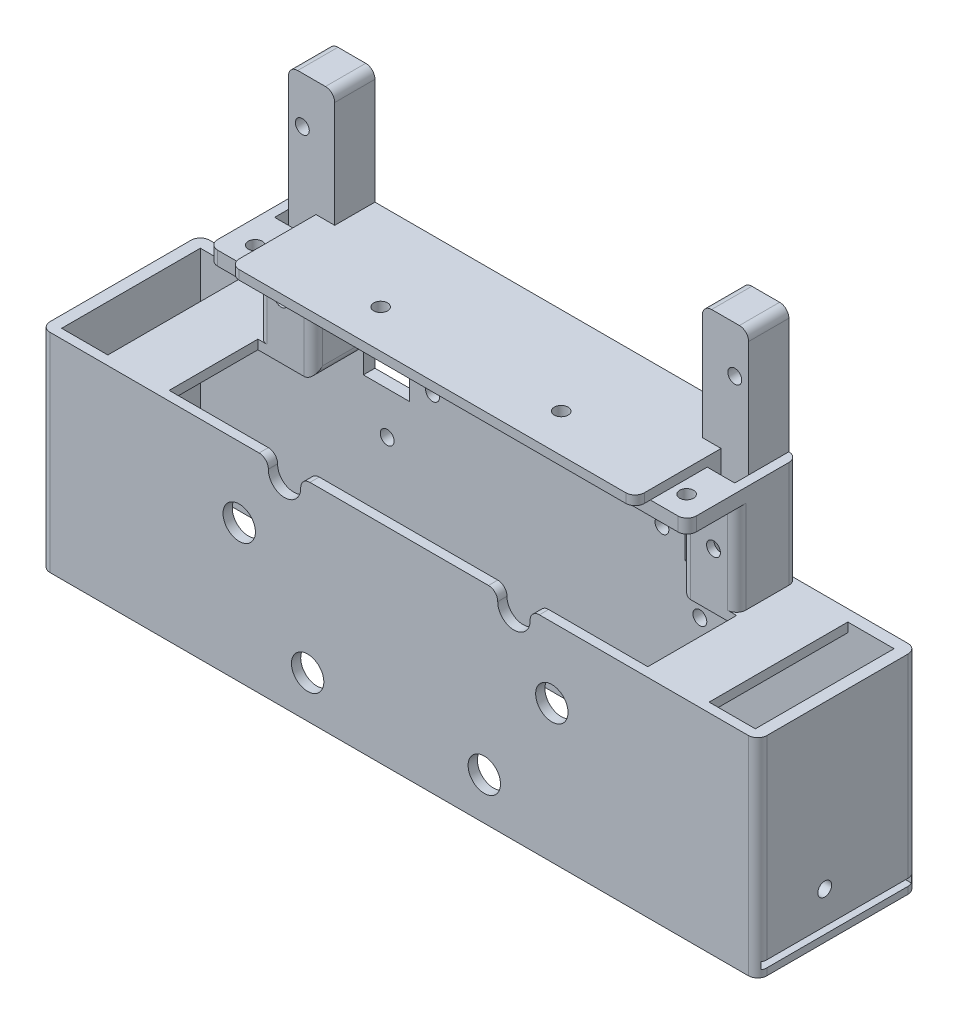
SolidWorks part; units mm, degrees
ref_plane "前视基准面" through (0, 0, 0) normal (0, 0, 1) x (1, 0, 0)
ref_plane "上视基准面" through (0, 0, 0) normal (0, 1, 0) x (1, 0, 0)
ref_plane "右视基准面" through (0, 0, 0) normal (1, 0, 0) x (0, 0, -1)
other "Configuration Table"
sketch "草图1" plane through (0, 0, 0) normal (0, 0, 1) x (1, 0, 0)
  line L0 (7.95, 3) -> (7.95, 5)
  line L1 (0, 0) -> (103.5, 0)
  line L2 (0, 0) -> (0, 3)
  line L3 (0, 3) -> (103.5, 3)
  line L4 (103.5, 0) -> (103.5, 3)
  line L5 (7.95, 5) -> (95.55, 5)
  line L6 (95.55, 5) -> (95.55, 3)
  line L7 (12, 3) -> (12, 30) construction
  line L8 (12, 30) -> (91.5, 30) construction
  line L9 (91.5, 30) -> (91.5, 3) construction
  line L10 (91.5, 30) -> (101.5, 30)
  line L11 (101.5, 30) -> (101.5, 3)
  line L12 (91.5, 30) -> (91.5, 5)
  line L13 (103.5, 0) -> (103.5, -46.5)
  line L14 (91.5, 0) -> (91.5, -46.5)
  line L15 (91.5, -46.5) -> (103.5, -46.5)
  line L16 (101.5, 3) -> (101.5, -46.5)
  line L17 (51.75, -46.5) -> (51.75, -16.5)
  line L18 (51.75, -16.5) -> (91.5, -16.5)
  line L19 (51.75, -46.5) -> (91.5, -46.5)
  line L20 (51.75, -16.5) -> (51.75, 0)
  line L21 (66.75, -16.5) -> (66.75, 0)
  line L22 (91.5, -16.5) -> (101.5, -16.5)
  line L23 (51.75, 5) -> (51.75, 0) construction
  line L24 (51.75, 5) -> (51.75, 0)
  line L25 (51.75, -20) -> (103.5, -20)
  line L26 (103.5, -20) -> (103.5, -65)
  line L27 (103.5, -65) -> (51.75, -65)
  line L28 (51.75, -65) -> (51.75, -20)
  line L29 (91.5, 5) -> (91.5, 0)
  line L30 (91.5, -46.5) -> (91.5, -65)
  line L31 (101.5, -46.5) -> (101.5, -65)
  line L32 (101.5, -16.5) -> (103.5, -16.5)
  line L33 (51.75, 5) -> (51.75, 30)
  line L34 (51.75, 30) -> (91.5, 30)
  point P7 (51.75, 5)
  point P10 (51.75, 3)
  point P14 (51.75, 30)
  dimension "D1" = 103.5
  dimension "D2" = 3
  dimension "D3" = 87.6
  dimension "D4" = 2
  dimension "D5" = 79.5
  dimension "D6" = 10
  dimension "D7" = 27
  dimension "D8" = 49.5
  dimension "D9" = 30
  dimension "D10" = 15
  dimension "D11" = 45
  dimension "D12" = 20
extrude "凸台-拉伸1" add sketch "草图1" along normal blind 19 contours L3 L29 L1 L16 | L3 L16 L1 L4 region at (96.5, 1.5, 0) region at (102.5, 1.5, 0)
extrude "凸台-拉伸2" add sketch "草图1<13>" along normal blind 13.2 from offset 5.8 contours L29 L3 L24 L1 region at (71.625, 1.5, 0)
sketch "草图1<13>" plane through (0, 0, 0) normal (0, 0, 1) x (1, 0, 0) same geometry as "草图1"
extrude "凸台-拉伸3" add sketch "草图1<14>" along normal blind 22.3 contours L5 L29 L3 L6 region at (93.525, 4, 0)
sketch "草图1<14>" plane through (0, 0, 0) normal (0, 0, 1) x (1, 0, 0) same geometry as "草图1"
extrude "凸台-拉伸4" add sketch "草图1<15>" along normal blind 16.5 from offset 5.8 contours L29 L5 L24 L3 region at (71.625, 4, 0)
sketch "草图1<15>" plane through (0, 0, 0) normal (0, 0, 1) x (1, 0, 0) same geometry as "草图1"
extrude "凸台-拉伸5" add sketch "草图1<16>" along normal blind 3.7 contours L10 L12 L5 L6 L3 L11 | L14 L22 L16 L1 | L14 L25 L16 L22 | L25 L14 L15 L16 | L16 L25 L13 L1 | L25 L16 L15 L13 | L15 L30 L27 L26 | L15 L31 L27 L26 | L32 L16 L25 L13 region at (96.592, 16.8866, 0) region at (96.5, -8.25, 0) region at (102.5, -8.25, 0) region at (96.5, -18.25, 0) region at (102.5, -18.25, 0) region at (96.5, -33.25, 0) region at (102.5, -33.25, 0) region at (96.5, -55.75, 0) region at (102.5, -55.75, 0)
sketch "草图1<16>" plane through (0, 0, 0) normal (0, 0, 1) x (1, 0, 0) same geometry as "草图1"
extrude "凸台-拉伸6" add sketch "草图1<20>" along normal blind 2.5 from surface contours L25 L17 L19 L14 | L30 L19 L28 L27 | L18 L21 L1 L20 | L17 L25 L14 L18 | L21 L18 L14 L1 region at (59.25, -8.25, 0) region at (79.125, -8.25, 0) region at (71.625, -18.25, 0) region at (71.625, -33.25, 0) region at (71.625, -55.75, 0) starting at face at (71.625, 2.5, 5.8)
sketch "草图1<20>" plane through (0, 0, 0) normal (0, 0, 1) x (1, 0, 0) same geometry as "草图1"
extrude "凸台-拉伸8" add sketch "草图1<23>" along normal up to surface (8.3 mm away) from surface contours L25 L14 L15 L16 | L31 L15 L30 L27 | L14 L25 L16 L22 | L32 L16 L25 L13 | L25 L16 L15 L13 | L15 L31 L27 L26 | L14 L22 L16 L1 | L16 L32 L13 L1 region at (96.5, -8.25, 0) region at (102.5, -8.25, 0) region at (96.5, -18.25, 0) region at (102.5, -18.25, 0) region at (96.5, -33.25, 0) region at (102.5, -33.25, 0) region at (96.5, -55.75, 0) region at (102.5, -55.75, 0) up to face at (71.625, -32.5, 8.3) starting at face at (97.5, -32.5, 3.7)
sketch "草图1<23>" plane through (0, 0, 0) normal (0, 0, 1) x (1, 0, 0) same geometry as "草图1"
sketch "草图2" plane through (0, -65, 0) normal (0, -1, 0) x (1, 0, 0)
  line L4 (51.75, 8.3) -> (103.5, 8.3)
  line L5 (103.5, 8.3) -> (103.5, 19)
  line L6 (91.5, 0) -> (103.5, 0)
  line L7 (103.5, 0) -> (103.5, 8.3)
  line L8 (103.5, 8.3) -> (51.75, 8.3)
  line L9 (51.75, 8.3) -> (51.75, 5.8)
  line L10 (51.75, 5.8) -> (91.5, 5.8)
  line L11 (91.5, 5.8) -> (91.5, 0)
  line L12 (91.5, 0) -> (103.5, 0)
  line L13 (103.5, 0) -> (103.5, 8.3)
  line L14 (103.5, 8.3) -> (51.75, 8.3)
  line L15 (51.75, 8.3) -> (51.75, 5.8)
  line L16 (51.75, 5.8) -> (91.5, 5.8)
  line L17 (91.5, 5.8) -> (91.5, 0)
  line L18 (103.5, 19) -> (51.75, 19)
  line L19 (51.75, 19) -> (51.75, 8.3)
  line L20 (51.75, 8.3) -> (103.5, 8.3)
  line L21 (103.5, 8.3) -> (103.5, 19)
  line L22 (103.5, 19) -> (51.75, 19)
  line L23 (51.75, 19) -> (51.75, 8.3)
  dimension "D2" = 8.3
  dimension "D1" = 0
  dimension "D3" = 0
extrude "凸台-拉伸9" add sketch "草图1<25>" along normal blind 2 from offset 27.5 separate body contours L25 L17 L19 L14 | L30 L19 L28 L27 | L31 L15 L30 L27 | L25 L14 L15 L16 region at (71.625, -33.25, 0) region at (96.5, -33.25, 0) region at (71.625, -55.75, 0) region at (96.5, -55.75, 0)
sketch "草图1<25>" plane through (0, 0, 0) normal (0, 0, 1) x (1, 0, 0) same geometry as "草图1"
sketch "草图3" plane through (0, 0, 29.5) normal (0, 0, 1) x (1, 0, 0)
  line L0 (101.5, -20) -> (126.75, -20)
  line L1 (126.75, -20) -> (126.75, -65)
  line L2 (126.75, -65) -> (101.5, -65)
  line L3 (126.75, -20) -> (129.25, -20)
  line L4 (51.75, -65) -> (101.5, -65)
  line L5 (101.5, -65) -> (101.5, -20)
  line L6 (101.5, -20) -> (51.75, -20)
  line L7 (51.75, -20) -> (51.75, -65)
  line L8 (51.75, -65) -> (101.5, -65)
  line L9 (101.5, -65) -> (101.5, -20)
  line L10 (101.5, -20) -> (51.75, -20)
  line L11 (51.75, -20) -> (51.75, -65)
  line L12 (129.25, -20) -> (129.25, -65)
  line L13 (129.25, -65) -> (126.75, -65)
  line M7 (101.5, -65) -> (101.5, -20)
  dimension "D2" = 75
  dimension "D3" = 2.5
  dimension "D1" = 0
extrude "凸台-拉伸11" add sketch "草图3" against normal up to surface (2 mm away) contours L2 L1 L0 M7 region at (114.125, -42.5, 29.5) up to face at (76.625, -42.5, 27.5)
extrude "凸台-拉伸12" add sketch "草图3<4>" against normal up to surface (29.5 mm away) contours L13 L12 L3 L1 region at (128, -42.5, 29.5) up to face at (98.8333, -10.6667, 0)
sketch "草图3<4>" plane through (0, 0, 29.5) normal (0, 0, 1) x (1, 0, 0) same geometry as "草图3"
sketch "草图5" plane through (129.25, 0, 0) normal (1, 0, 0) x (0, 0, -1)
  line L4 (-29.5, -65) -> (0, -65)
  line L5 (0, -65) -> (0, -20)
  line L6 (0, -20) -> (-29.5, -20)
  line L7 (-29.5, -20) -> (-29.5, -65)
  line L8 (-29.5, -65) -> (0, -65)
  line L9 (0, -65) -> (0, -20)
  line L10 (0, -20) -> (-29.5, -20)
  line L11 (-29.5, -20) -> (-29.5, -65)
  line L16 (0, -65) -> (0, 3)
  line L17 (0, 3) -> (-19, 3)
  line L18 (-19, 3) -> (-19, 0)
  line L19 (-19, 0) -> (-8.3, 0)
  line L22 (-8.3, 0) -> (-8.3, -65)
  line L23 (-8.3, -65) -> (0, -65)
  line L24 (0, -65) -> (0, 3)
  line L25 (0, 3) -> (-19, 3)
  line L26 (-19, 3) -> (-19, 0)
  line L27 (-19, 0) -> (-8.3, 0)
  line L30 (-8.3, 0) -> (-8.3, -65)
  line L31 (-8.3, -65) -> (0, -65)
  line M14 (0, -65) -> (0, -20)
  line M15 (0, -20) -> (-29.5, -20)
  dimension "D1" = 0
  dimension "D2" = 0
extrude "凸台-拉伸13" add sketch "草图5" against normal up to surface (25.75 mm away) from surface contours L30 L8 M15 M14 region at (129.25, -42.5, 4.15) up to face at (103.5, -20.6667, 9.1) starting at face at (126.75, -42.5, 13.75)
sketch "草图6" plane through (0, 5, 0) normal (0, 1, 0) x (1, 0, 0)
  line L0 (51.75, -14) -> (103.5, -14) construction
  line L1 (95.55, -6.7) -> (101.5, -6.7)
  line L3 (101.5, -6.7) -> (101.5, -3.7)
  line L6 (95.55, -3.7) -> (91.5, -3.7)
  line L7 (91.5, -3.7) -> (91.5, -5.8)
  line L8 (91.5, -5.8) -> (51.75, -5.8)
  line L9 (51.75, -5.8) -> (51.75, -22.3)
  line L10 (51.75, -22.3) -> (95.55, -22.3)
  line L11 (95.55, -22.3) -> (95.55, -3.7)
  line L12 (95.55, -3.7) -> (91.5, -3.7)
  line L13 (91.5, -3.7) -> (91.5, -5.8)
  line L14 (91.5, -5.8) -> (51.75, -5.8)
  line L15 (51.75, -5.8) -> (51.75, -22.3)
  line L16 (51.75, -22.3) -> (95.55, -22.3)
  line L17 (95.55, -22.3) -> (95.55, -3.7)
  line L18 (101.5, 0) -> (101.5, -3.7)
  line L19 (101.5, -3.7) -> (95.55, -3.7)
  line L20 (95.55, -3.7) -> (95.55, -19)
  line L21 (95.55, -19) -> (103.5, -19)
  line L22 (103.5, -19) -> (103.5, 0)
  line L23 (103.5, 0) -> (101.5, 0)
  line L24 (101.5, 0) -> (101.5, -3.7)
  line L25 (101.5, -3.7) -> (95.55, -3.7)
  line L26 (95.55, -3.7) -> (95.55, -19)
  line L27 (95.55, -19) -> (103.5, -19)
  line L28 (103.5, -19) -> (103.5, 0)
  line L29 (103.5, 0) -> (101.5, 0)
  circle A0 centre (71.27, -14) radius 1.5
  circle A1 centre (98.39, -14) radius 1.5
  line M18 (95.55, -22.3) -> (95.55, -3.7)
  dimension "D5" = 3
  dimension "D6" = 3
  dimension "D3" = 8.3
  dimension "D4" = 8.2
  dimension "D7" = 19.52
  dimension "D8" = 27.12
  dimension "D9" = 3
  dimension "D1" = 0
  dimension "D2" = 0
extrude "切除-拉伸1" cut sketch "草图6" against normal up to next contours A0 L0 | L0 A0 | A1 L0 | L0 A1 | L3 L25 L1 M18 region at (98.39, 5, 14.6366) region at (98.39, 5, 13.3634) region at (71.27, 5, 14.6366) region at (71.27, 5, 13.3634) region at (98.525, 5, 5.2)
ref_plane "基准面1" through (51.75, 0, 0) normal (-1, 0, 0) x (0, 0, 1)
sketch "草图7" plane through (0, -20, 0) normal (0, 1, 0) x (1, 0, 0)
  line L0 (103.5, -8.3) -> (103.5, -27.5)
  line L1 (116.75, -8.3) -> (116.75, -27.5)
  line L8 (103.5, 0) -> (103.5, -8.3)
  line L9 (103.5, -8.3) -> (126.75, -8.3)
  line L10 (126.75, -8.3) -> (126.75, -27.5)
  line L11 (126.75, -27.5) -> (51.75, -27.5)
  line L12 (51.75, -27.5) -> (51.75, -29.5)
  line L13 (51.75, -29.5) -> (129.25, -29.5)
  line L14 (129.25, -29.5) -> (129.25, 0)
  line L15 (129.25, 0) -> (103.5, 0)
  line L16 (103.5, 0) -> (103.5, -8.3)
  line L17 (103.5, -8.3) -> (126.75, -8.3)
  line L18 (126.75, -8.3) -> (126.75, -27.5)
  line L19 (126.75, -27.5) -> (51.75, -27.5)
  line L20 (51.75, -27.5) -> (51.75, -29.5)
  line L21 (51.75, -29.5) -> (129.25, -29.5)
  line L22 (129.25, -29.5) -> (129.25, 0)
  line L23 (129.25, 0) -> (103.5, 0)
  line M11 (103.5, -8.3) -> (126.75, -8.3)
  line M13 (126.75, -27.5) -> (51.75, -27.5)
  dimension "D2" = 10
  dimension "D1" = 0
extrude "凸台-拉伸14" add sketch "草图7" against normal blind 2 contours L1 L0 M11 M13 region at (110.125, -20, 17.9)
sketch "草图9" plane through (0, 0, 0) normal (0, 0, -1) x (-1, 0, 0)
  line L7 (-51.75, -5) -> (-76.55, -5) construction
  line L8 (-101.5, 30) -> (-101.5, 3)
  line L9 (-101.5, 3) -> (-103.5, 3)
  line L10 (-103.5, 3) -> (-103.5, -20)
  line L11 (-103.5, -20) -> (-129.25, -20)
  line L12 (-129.25, -20) -> (-129.25, -65)
  line L13 (-129.25, -65) -> (-91.5, -65)
  line L14 (-91.5, -65) -> (-91.5, 30)
  line L15 (-91.5, 30) -> (-101.5, 30)
  line L16 (-101.5, 30) -> (-101.5, 3)
  line L17 (-101.5, 3) -> (-103.5, 3)
  line L18 (-103.5, 3) -> (-103.5, -20)
  line L19 (-103.5, -20) -> (-129.25, -20)
  line L20 (-129.25, -20) -> (-129.25, -65)
  line L21 (-129.25, -65) -> (-91.5, -65)
  line L22 (-91.5, -65) -> (-91.5, 30)
  line L23 (-91.5, 30) -> (-101.5, 30)
  line L24 (-76.55, -5) -> (-76.55, -22.1) construction
  line L25 (-76.55, -22.1) -> (-51.75, -22.1) construction
  line L26 (-91.5, -26.1) -> (-51.75, -26.1) construction
  line L28 (-91.5, 5) -> (-91.5, -65)
  line L33 (-91.5, -65) -> (-51.75, -65)
  line L34 (-51.75, -65) -> (-51.75, 5)
  line L35 (-51.75, 5) -> (-91.5, 5)
  line L36 (-91.5, 5) -> (-91.5, -65)
  line L41 (-91.5, -65) -> (-51.75, -65)
  line L42 (-51.75, -65) -> (-51.75, 5)
  line L43 (-51.75, 5) -> (-91.5, 5)
  circle A4 centre (-76.55, -5) radius 1.5
  circle A5 centre (-76.55, -22.1) radius 1.5
  dimension "D13" = 3
  dimension "D14" = 3
  dimension "D15" = 10
  dimension "D16" = 17.1
  dimension "D17" = 24.8
  dimension "D18" = 4
  dimension "D1" = 0
  dimension "D7" = 0
sketch "草图17" plane through (0, 0, 27.5) normal (0, 0, -1) x (-1, 0, 0)
  line L1 (-103.5, -22) -> (-51.75, -22)
  line L9 (-51.75, -65) -> (-51.75, -20)
  line L10 (-51.75, -65) -> (-51.75, -20)
  line L15 (-51.75, -20) -> (-103.5, -20)
  line L16 (-103.5, -20) -> (-103.5, -22)
  line L17 (-103.5, -22) -> (-116.75, -22)
  line L18 (-116.75, -22) -> (-116.75, -20)
  line L19 (-116.75, -20) -> (-126.75, -20)
  line L20 (-126.75, -20) -> (-126.75, -65)
  line L21 (-126.75, -65) -> (-51.75, -65)
  line L29 (-51.75, -20) -> (-103.5, -20)
  line L30 (-103.5, -20) -> (-103.5, -22)
  line L31 (-103.5, -22) -> (-116.75, -22)
  line L32 (-116.75, -22) -> (-116.75, -20)
  line L33 (-116.75, -20) -> (-126.75, -20)
  line L34 (-126.75, -20) -> (-126.75, -65)
  line L35 (-126.75, -65) -> (-51.75, -65)
  line M22 (-103.5, -22) -> (-116.75, -22)
  line M23 (-116.75, -22) -> (-116.75, -20)
  line M24 (-116.75, -20) -> (-126.75, -20)
  line M25 (-126.75, -20) -> (-126.75, -65)
  line M26 (-126.75, -65) -> (-51.75, -65)
  line M52 (-51.75, -65) -> (-51.75, -20)
  dimension "D1" = 0
extrude "凸台-拉伸15" add sketch "草图1<29>" along normal up to surface (5.8 mm away) contours L34 L33 L5 L12 | L30 L19 L28 L27 | L25 L17 L19 L14 | L21 L18 L14 L1 | L18 L21 L1 L20 | L29 L3 L24 L1 | L29 L5 L24 L3 | L17 L25 L14 L18 region at (71.625, 4, 0) region at (71.625, 1.5, 0) region at (71.625, 17.5, 0) region at (59.25, -8.25, 0) region at (79.125, -8.25, 0) region at (71.625, -18.25, 0) region at (71.625, -33.25, 0) region at (71.625, -55.75, 0) up to face at (71.625, -30, 5.8)
sketch "草图1<29>" plane through (0, 0, 0) normal (0, 0, 1) x (1, 0, 0) same geometry as "草图1"
extrude "切除-拉伸10" cut sketch "草图17" along normal blind 5.8 from surface contours L1 M22 M23 M24 M25 M26 M52 region at (89.4503, -43.3613, 27.5) starting at face at (100.1111, -26, 8.3)
extrude "切除-拉伸12" cut sketch "草图9" against normal through all contours A4 | A5 region at (76.55, -5, 0) region at (76.55, -22.1, 0)
sketch "草图21" plane through (0, 0, 0) normal (0, 0, -1) x (-1, 0, 0)
  line L8 (-101.5, 30) -> (-101.5, 3)
  line L9 (-101.5, 3) -> (-103.5, 3)
  line L10 (-103.5, 3) -> (-103.5, -20)
  line L11 (-103.5, -20) -> (-129.25, -20)
  line L12 (-129.25, -20) -> (-129.25, -65)
  line L13 (-129.25, -65) -> (-51.75, -65)
  line L14 (-51.75, -65) -> (-51.75, 30)
  line L15 (-51.75, 30) -> (-101.5, 30)
  line L16 (-101.5, 30) -> (-101.5, 3)
  line L17 (-101.5, 3) -> (-103.5, 3)
  line L18 (-103.5, 3) -> (-103.5, -20)
  line L19 (-103.5, -20) -> (-129.25, -20)
  line L20 (-129.25, -20) -> (-129.25, -65)
  line L21 (-129.25, -65) -> (-51.75, -65)
  line L22 (-51.75, -65) -> (-51.75, 30)
  line L23 (-51.75, 30) -> (-101.5, 30)
  circle A3 centre (-76.55, -22.1) radius 1.5 construction
  circle A4 centre (-76.55, -5) radius 1.5 construction
  circle A9 centre (-76.55, -22.1) radius 1.5
  circle A10 centre (-76.55, -5) radius 1.5
  dimension "D1" = 0
extrude "凸台-拉伸16" add sketch "草图21" along normal blind 5
extrude "切除-拉伸14" cut sketch "草图17<10>" along normal blind 5 from surface contours L1 M22 M23 M24 M25 M26 M52 region at (89.4503, -43.3613, 27.5) starting at face at (92.95, -32.45, 2.5)
sketch "草图17<10>" plane through (0, 0, 27.5) normal (0, 0, -1) x (-1, 0, 0) same geometry as "草图17"
sketch "草图24" plane through (0, 0, 8.3) normal (0, 0, 1) x (1, 0, 0)
  line L1 (95.55, -22) -> (101.5, -22) construction
  line L2 (101.5, -22) -> (101.5, 3) construction
  line L3 (101.5, 3) -> (101.5, 30) construction
  line L4 (101.5, 30) -> (91.5, 30) construction
  line L5 (91.5, 30) -> (91.5, 5) construction
  line L6 (78.0467, -22) -> (103.5, -22)
  line L7 (103.5, -22) -> (103.5, -20)
  line L8 (103.5, -20) -> (103.5, 0)
  line L9 (103.5, 0) -> (51.75, 0)
  line L10 (51.75, 0) -> (51.75, -22)
  line L11 (51.75, -22) -> (75.0533, -22)
  line L12 (78.0467, -22) -> (103.5, -22)
  line L13 (103.5, -22) -> (103.5, -20)
  line L14 (103.5, -20) -> (103.5, 0)
  line L15 (103.5, 0) -> (51.75, 0)
  line L16 (51.75, 0) -> (51.75, -22)
  line L17 (51.75, -22) -> (75.0533, -22)
  line L18 (91.5, 5) -> (95.55, 5) construction
  line L19 (95.55, 5) -> (95.55, -22) construction
  line L20 (95.55, 5) -> (51.75, 5) construction
  line L21 (51.75, 5) -> (51.75, 3) construction
  line L22 (51.75, 3) -> (95.55, 3) construction
  line L23 (95.55, 3) -> (95.55, 5) construction
  line L24 (95.55, 3) -> (51.75, 3) construction
  line L25 (51.75, 3) -> (51.75, 0) construction
  line L26 (51.75, 0) -> (103.5, 0) construction
  line L27 (103.5, 0) -> (103.5, 3) construction
  line L28 (103.5, 3) -> (95.55, 3) construction
  line L29 (51.75, 30) -> (51.75, 5) construction
  line L30 (51.75, 5) -> (91.5, 5) construction
  line L31 (91.5, 5) -> (91.5, 30) construction
  line L32 (91.5, 30) -> (51.75, 30) construction
  line L33 (95.55, -22) -> (101.5, -22)
  line L34 (101.5, -22) -> (101.5, 3)
  line L35 (101.5, 3) -> (101.5, 30)
  line L36 (101.5, 30) -> (91.5, 30)
  line L37 (91.5, 30) -> (91.5, 5)
  line L38 (91.5, 5) -> (95.55, 5)
  line L39 (95.55, 5) -> (95.55, -22)
  line L40 (95.55, 5) -> (51.75, 5)
  line L41 (51.75, 5) -> (51.75, 3)
  line L42 (51.75, 3) -> (95.55, 3)
  line L43 (95.55, 3) -> (95.55, 5)
  line L44 (95.55, 3) -> (51.75, 3)
  line L45 (51.75, 3) -> (51.75, 0)
  line L46 (51.75, 0) -> (103.5, 0)
  line L47 (103.5, 0) -> (103.5, 3)
  line L48 (103.5, 3) -> (95.55, 3)
  line L49 (51.75, 30) -> (51.75, 5)
  line L50 (51.75, 5) -> (91.5, 5)
  line L51 (91.5, 5) -> (91.5, 30)
  line L52 (91.5, 30) -> (51.75, 30)
  line L53 (91.5, 0) -> (91.5, -22)
  circle A0 centre (76.55, -5) radius 1.5 construction
  arc A1 (78.0467, -22) -> (75.0533, -22) centre (76.55, -22.1) ccw
  arc A2 (78.0467, -22) -> (75.0533, -22) centre (76.55, -22.1) ccw
  circle A3 centre (76.55, -5) radius 1.5
  circle M9 centre (76.55, -5) radius 1.5
  arc M10 (75.0533, -22) -> (78.0467, -22) centre (76.55, -22.1) cw
  line M11 (78.0467, -22) -> (103.5, -22)
  line M14 (103.5, 0) -> (51.75, 0)
  line M15 (51.75, 0) -> (51.75, -22)
  line M16 (51.75, -22) -> (75.0533, -22)
  dimension "D1" = 0
extrude "切除-拉伸16" cut sketch "草图24" against normal up to surface (10.8 mm away) contours M14 M15 M16 M10 M11 M9 region at (71.5663, -11.0101, 8.3) up to face at (92.95, -32.45, -2.5)
sketch "草图23" plane through (129.25, 0, 0) normal (1, 0, 0) x (0, 0, -1)
  line L0 (5, -55) -> (-15, -55) construction
  line L4 (-29.5, -65) -> (5, -65)
  line L5 (5, -65) -> (5, -20)
  line L6 (5, -20) -> (-29.5, -20)
  line L7 (-29.5, -20) -> (-29.5, -65)
  line L8 (-29.5, -65) -> (5, -65)
  line L9 (5, -65) -> (5, -20)
  line L10 (5, -20) -> (-29.5, -20)
  line L11 (-29.5, -20) -> (-29.5, -65)
  circle A0 centre (-15, -55) radius 1.5
  dimension "D4" = 3
  dimension "D2" = 20
  dimension "D3" = 10
  dimension "D1" = 0
extrude "切除-拉伸15" cut sketch "草图23" against normal up to next contours A0 region at (129.25, -55, 15)
fillet "圆角1" radius 2 10 edges at (71.625, 30, 5.8) (129.25, -42.5, 29.5) (129.25, -42.5, -5) (103.5, -8.5, -5) (95.55, 4, 22.3) (103.5, 1.5, 19) (101.5, 30, -0.65) (103.5, -10, 8.3) (91.5, -11, 8.3) (91.5, -22, 2.9)
mirror "镜向2" about plane through (51.75, 0, 0) normal (-1, 0, 0) of bodies 141 135
sketch "草图25" plane through (0, 0, -5) normal (0, 0, -1) x (-1, 0, 0)
  line L0 (-91.65, -26.1) -> (-11.85, -26.1) construction
  line L1 (-91.65, -26.1) -> (-91.65, -63.8) construction
  line L2 (-91.65, -63.8) -> (-11.85, -63.8) construction
  line L3 (-11.85, -63.8) -> (-11.85, -26.1) construction
  line L4 (-91.5, -1) -> (-81.5, -1)
  line L5 (-51.75, -67.2669) -> (-51.75, 67.2669) construction
  line L6 (0, 3) -> (-2, 3) construction
  line L7 (-2, 3) -> (-2, -20) construction
  line L8 (0, -20) -> (-2, -20) construction
  line L9 (0, -20) -> (0, 3) construction
  line L10 (-101.5, -20) -> (-127.25, -20)
  line L11 (-127.25, -20) -> (-127.25, -65)
  line L12 (-127.25, -65) -> (23.75, -65)
  line L13 (23.75, -65) -> (23.75, -20)
  line L14 (23.75, -20) -> (-2, -20)
  line L15 (-2, -20) -> (-2, 3)
  line L16 (-2, 3) -> (-2, 28)
  line L17 (-4, 30) -> (-99.5, 30)
  line L18 (-101.5, 28) -> (-101.5, 3)
  line L19 (-101.5, 3) -> (-101.5, -20)
  line L20 (-101.5, -20) -> (-127.25, -20)
  line L21 (-127.25, -20) -> (-127.25, -65)
  line L22 (-127.25, -65) -> (23.75, -65)
  line L23 (23.75, -65) -> (23.75, -20)
  line L24 (23.75, -20) -> (-2, -20)
  line L25 (-2, -20) -> (-2, 3)
  line L26 (-2, 3) -> (-2, 28)
  line L27 (-4, 30) -> (-99.5, 30)
  line L28 (-101.5, 28) -> (-101.5, 3)
  line L29 (-101.5, 3) -> (-101.5, -20)
  line L30 (-101.5, 3) -> (-103.5, 3) construction
  line L31 (-103.5, 3) -> (-103.5, -20) construction
  line L32 (-101.5, -20) -> (-103.5, -20) construction
  line L33 (-101.5, -20) -> (-101.5, 3) construction
  line L34 (0, 3) -> (-2, 3)
  line L35 (-2, 3) -> (-2, -20)
  line L36 (0, -20) -> (-2, -20)
  line L37 (0, -20) -> (0, 3)
  line L38 (-101.5, 3) -> (-103.5, 3)
  line L39 (-103.5, 3) -> (-103.5, -20)
  line L40 (-101.5, -20) -> (-103.5, -20)
  line L41 (-101.5, -20) -> (-101.5, 3)
  line L42 (-91.5, 30) -> (-91.5, 5)
  line L43 (-91.5, 5) -> (-12, 5)
  line L44 (-12, 5) -> (-12, 30)
  line L45 (-81.5, -1) -> (-81.5, -26.1)
  line L46 (-81.5, -26.1) -> (-91.5, -26.1)
  line L47 (-91.5, -26.1) -> (-91.5, -1)
  line L48 (-22, -1) -> (-22, -26.1)
  line L49 (-22, -26.1) -> (-12, -26.1)
  line L50 (-12, -26.1) -> (-12, -1)
  line L51 (-12, -1) -> (-22, -1)
  circle A0 centre (-26.95, -22.1) radius 1.5 construction
  circle A1 centre (-26.95, -5) radius 1.5 construction
  arc A2 (-2, 28) -> (-4, 30) centre (-4, 28) ccw
  arc A3 (-99.5, 30) -> (-101.5, 28) centre (-99.5, 28) ccw
  arc A4 (-2, 28) -> (-4, 30) centre (-4, 28) ccw
  arc A5 (-99.5, 30) -> (-101.5, 28) centre (-99.5, 28) ccw
  circle A6 centre (-76.55, -5) radius 1.5 construction
  circle A7 centre (-76.55, -22.1) radius 1.5 construction
  circle A8 centre (-26.95, -22.1) radius 1.5
  circle A9 centre (-26.95, -5) radius 1.5
  circle A10 centre (-76.55, -5) radius 1.5
  circle A11 centre (-76.55, -22.1) radius 1.5
  circle A12 centre (-84.75, -35.2) radius 1.5
  circle A13 centre (-17.15, -35.2) radius 1.5
  circle A14 centre (-31.95, -55.9) radius 1.5
  circle A15 centre (-70.15, -55.9) radius 1.5
  circle A16 centre (-98.5, 20) radius 1.5
  circle A17 centre (-98.5, -10) radius 1.5
  circle A18 centre (-5, 20) radius 1.5
  circle A19 centre (-5, -10) radius 1.5
  point P38 (-51.75, -26.1)
  point P48 (-51.75, 5)
  point P66 (0, 0)
  point P67 (0, 0)
  dimension "D4" = 3
  dimension "D5" = 3
  dimension "D6" = 3
  dimension "D7" = 3
  dimension "D20" = 10
  dimension "D21" = 3
  dimension "D22" = 3
  dimension "D23" = 3
  dimension "D24" = 3
  dimension "D2" = 79.8
  dimension "D3" = 37.7
  dimension "D8" = 6.9
  dimension "D9" = 9.1
  dimension "D10" = 5.3
  dimension "D11" = 20.1
  dimension "D12" = 21.5
  dimension "D13" = 7.9
  dimension "D14" = 4
  dimension "D15" = 25
  dimension "D16" = 79.5
  dimension "D17" = 4
  dimension "D18" = 4
  dimension "D19" = 10
  dimension "D25" = 10
  dimension "D26" = 30
  dimension "D27" = 3
  dimension "D28" = 3
  dimension "D1" = 0
sketch "草图27" plane through (0, 0, -2.5) normal (0, 0, 1) x (1, 0, 0)
  line L12 (91.5, 0) -> (12, 0)
  line L13 (12, 0) -> (12, -20)
  line L14 (10, -22) -> (-13.25, -22)
  line L15 (-13.25, -22) -> (-13.25, -20)
  line L16 (-13.25, -20) -> (-23.25, -20)
  line L17 (-23.25, -20) -> (-23.25, -65)
  line L18 (-23.25, -65) -> (126.75, -65)
  line L19 (126.75, -65) -> (126.75, -20)
  line L20 (126.75, -20) -> (116.75, -20)
  line L21 (116.75, -20) -> (116.75, -22)
  line L22 (116.75, -22) -> (93.5, -22)
  line L23 (91.5, -20) -> (91.5, 0)
  line L24 (91.5, 0) -> (12, 0)
  line L25 (12, 0) -> (12, -20)
  line L26 (10, -22) -> (-13.25, -22)
  line L27 (-13.25, -22) -> (-13.25, -20)
  line L28 (-13.25, -20) -> (-23.25, -20)
  line L29 (-23.25, -20) -> (-23.25, -65)
  line L30 (-23.25, -65) -> (126.75, -65)
  line L31 (126.75, -65) -> (126.75, -20)
  line L32 (126.75, -20) -> (116.75, -20)
  line L33 (116.75, -20) -> (116.75, -22)
  line L34 (116.75, -22) -> (93.5, -22)
  line L35 (91.5, -20) -> (91.5, 0)
  arc A2 (10, -22) -> (12, -20) centre (10, -20) ccw
  arc A3 (10, -22) -> (12, -20) centre (10, -20) ccw
  arc A4 (91.5, -20) -> (93.5, -22) centre (93.5, -20) ccw
  arc A5 (91.5, -20) -> (93.5, -22) centre (93.5, -20) ccw
  dimension "D1" = 0
extrude "切除-拉伸17" cut sketch "草图25" against normal up to next contours L47 L46 L45 L4 | L50 L51 L48 L49 | L43 L44 L27 L42 region at (86.5, -13.55, -5) region at (51.75, 17.5, -5) region at (17, -13.55, -5)
extrude "切除-拉伸18" cut sketch "草图25<4>" against normal through all contours A13 | A14 | A12 | A15 region at (84.75, -35.2, -5) region at (17.15, -35.2, -5) region at (31.95, -55.9, -5) region at (70.15, -55.9, -5)
sketch "草图25<4>" plane through (0, 0, -5) normal (0, 0, -1) x (-1, 0, 0) same geometry as "草图25"
sketch "草图28" plane through (0, 0, 27.5) normal (0, 0, -1) x (-1, 0, 0)
  line L12 (-116.75, -22) -> (-116.75, -20)
  line L13 (-116.75, -20) -> (-126.75, -20)
  line L14 (-126.75, -20) -> (-126.75, -65)
  line L15 (-126.75, -65) -> (23.25, -65)
  line L16 (23.25, -65) -> (23.25, -20)
  line L17 (23.25, -20) -> (13.25, -20)
  line L18 (13.25, -20) -> (13.25, -22)
  line L19 (13.25, -22) -> (0, -22)
  line L20 (0, -22) -> (0, -20)
  line L21 (0, -20) -> (-103.5, -20)
  line L22 (-103.5, -20) -> (-103.5, -22)
  line L23 (-103.5, -22) -> (-116.75, -22)
  line L24 (-116.75, -22) -> (-116.75, -20)
  line L25 (-116.75, -20) -> (-126.75, -20)
  line L26 (-126.75, -20) -> (-126.75, -65)
  line L27 (-126.75, -65) -> (23.25, -65)
  line L28 (23.25, -65) -> (23.25, -20)
  line L29 (23.25, -20) -> (13.25, -20)
  line L30 (13.25, -20) -> (13.25, -22)
  line L31 (13.25, -22) -> (0, -22)
  line L32 (0, -22) -> (0, -20)
  line L33 (0, -20) -> (-103.5, -20)
  line L34 (-103.5, -20) -> (-103.5, -22)
  line L35 (-103.5, -22) -> (-116.75, -22)
  circle A0 centre (-76.55, -22.1) radius 1.5 construction
  circle A1 centre (-26.95, -22.1) radius 1.5 construction
  circle A2 centre (-17.15, -35.2) radius 1.5 construction
  circle A3 centre (-31.95, -55.9) radius 1.5 construction
  circle A4 centre (-70.15, -55.9) radius 1.5 construction
  circle A5 centre (-84.75, -35.2) radius 1.5 construction
  circle A6 centre (-76.55, -22.1) radius 1.5
  circle A7 centre (-26.95, -22.1) radius 1.5
  circle A8 centre (-17.15, -35.2) radius 1.5
  circle A9 centre (-31.95, -55.9) radius 1.5
  circle A10 centre (-70.15, -55.9) radius 1.5
  circle A11 centre (-84.75, -35.2) radius 1.5
  circle A12 centre (-76.55, -22.1) radius 3.5
  circle A13 centre (-84.75, -35.2) radius 3.5
  circle A14 centre (-70.15, -55.9) radius 3.5
  circle A15 centre (-31.95, -55.9) radius 3.5
  circle A16 centre (-17.15, -35.2) radius 3.5
  circle A17 centre (-26.95, -22.1) radius 3.5
  circle M13 centre (-17.15, -35.2) radius 1.5
  circle M14 centre (-70.15, -55.9) radius 1.5
  circle M15 centre (-84.75, -35.2) radius 1.5
  circle M16 centre (-31.95, -55.9) radius 1.5
  circle M17 centre (-76.55, -22.1) radius 1.5
  circle M30 centre (-26.95, -22.1) radius 1.5
  dimension "D2" = 7
  dimension "D3" = 7
  dimension "D4" = 7
  dimension "D5" = 7
  dimension "D6" = 7
  dimension "D7" = 7
  dimension "D1" = 0
extrude "切除-拉伸19" cut sketch "草图28" against normal up to next contours L33 A12 M17 | A13 M15 | A14 M14 | A15 M16 | A16 M13 | L33 A17 M30 region at (76.55, -20.0896, 27.5) region at (26.95, -20.0896, 27.5) region at (88.151, -35.2, 27.5) region at (73.551, -55.9, 27.5) region at (35.351, -55.9, 27.5) region at (20.551, -35.2, 27.5)
fillet "圆角2" radius 2 6 edges at (73.75, -20, 28.5) (79.35, -20, 28.5) (29.75, -20, 28.5) (24.15, -20, 28.5) (91.5, 30, -0.65) (12, 30, -0.65)
extrude "切除-拉伸20" cut sketch "草图25<5>" against normal through all contours A16 | A17 | A18 | A19 region at (98.5, 20, -5) region at (98.5, -10, -5) region at (5, 20, -5) region at (5, -10, -5)
sketch "草图25<5>" plane through (0, 0, -5) normal (0, 0, -1) x (-1, 0, 0) same geometry as "草图25"
sketch "草图29" plane through (0, -65, 0) normal (0, -1, 0) x (1, 0, 0)
  line L0 (126.75, -2.5) -> (126.75, 27.5) construction
  line L1 (-23.25, -2.5) -> (126.75, -2.5) construction
  line L2 (-23.25, -2.5) -> (-23.25, 27.5) construction
  line L3 (126.75, 27.5) -> (-23.25, 27.5) construction
  line L4 (-23.75, -5) -> (127.25, -5)
  line L5 (129.25, -3) -> (129.25, 27.5)
  line L6 (127.25, 29.5) -> (-23.75, 29.5)
  line L7 (-25.75, 27.5) -> (-25.75, -3)
  line L8 (-23.75, -5) -> (127.25, -5)
  line L9 (129.25, -3) -> (129.25, 27.5)
  line L10 (127.25, 29.5) -> (-23.75, 29.5)
  line L11 (-25.75, 27.5) -> (-25.75, -3)
  line L12 (126.75, -2.5) -> (126.75, 27.5)
  line L13 (-23.25, -2.5) -> (126.75, -2.5)
  line L14 (-23.25, -2.5) -> (-23.25, 27.5)
  line L15 (126.75, 27.5) -> (-23.25, 27.5)
  line L16 (-23.25, 27.5) -> (-23.25, 28.5)
  line L17 (-23.25, 28.5) -> (129.25, 28.5)
  line L18 (129.25, 28.5) -> (129.25, -4)
  line L19 (129.25, -4) -> (-23.25, -4)
  line L20 (-23.25, -4) -> (-23.25, -2.5)
  arc A4 (-25.75, -3) -> (-23.75, -5) centre (-23.75, -3) ccw
  arc A5 (127.25, -5) -> (129.25, -3) centre (127.25, -3) ccw
  arc A6 (129.25, 27.5) -> (127.25, 29.5) centre (127.25, 27.5) ccw
  arc A7 (-23.75, 29.5) -> (-25.75, 27.5) centre (-23.75, 27.5) ccw
  arc A8 (-25.75, -3) -> (-23.75, -5) centre (-23.75, -3) ccw
  arc A9 (127.25, -5) -> (129.25, -3) centre (127.25, -3) ccw
  arc A10 (129.25, 27.5) -> (127.25, 29.5) centre (127.25, 27.5) ccw
  arc A11 (-23.75, 29.5) -> (-25.75, 27.5) centre (-23.75, 27.5) ccw
  arc M20 (127.25, -5) -> (129.25, -3) centre (127.25, -3) ccw
  line M21 (129.25, -3) -> (129.25, 27.5)
  arc M22 (129.25, 27.5) -> (127.25, 29.5) centre (127.25, 27.5) ccw
  line M26 (126.75, -2.5) -> (-23.25, -2.5)
  line M28 (-23.25, 27.5) -> (126.75, 27.5)
  line M29 (126.75, 27.5) -> (126.75, -2.5)
  dimension "D2" = 1
  dimension "D3" = 1
  dimension "D1" = 0
extrude "切除-拉伸24" cut sketch "草图29" against normal blind 1.5 from offset 1.5 contours L20 L19 L17 L16 M20 M21 M22 M28 M29 M26 region at (52.866, -65, -3.8441) offset against normal yes
